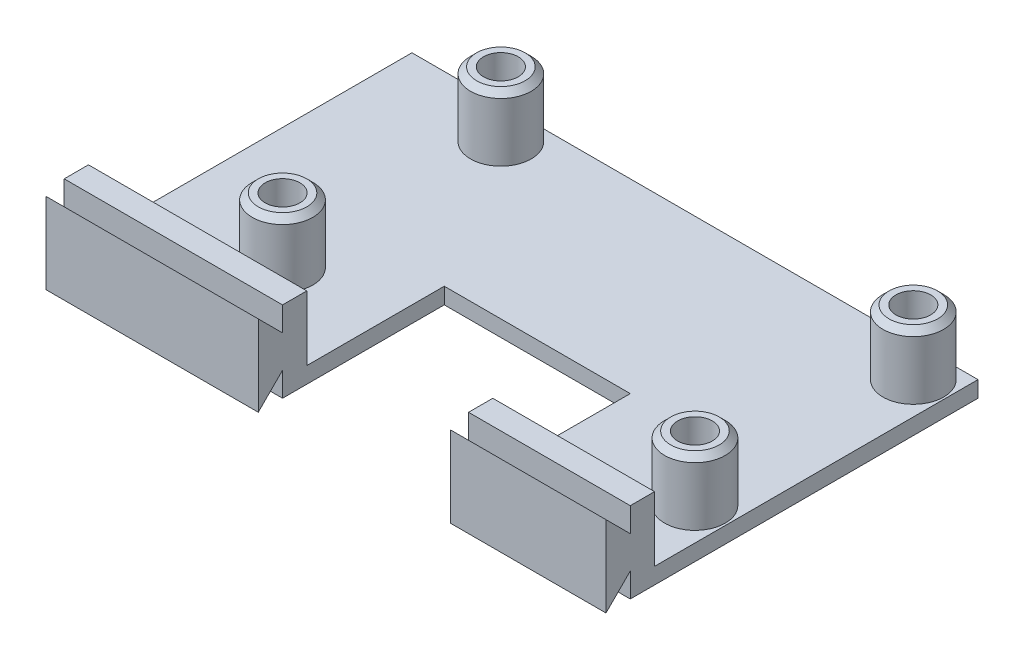
SolidWorks part; units mm, degrees
ref_plane "Front Plane" through (0, 0, 0) normal (0, 0, 1) x (1, 0, 0)
ref_plane "Top Plane" through (0, 0, 0) normal (0, 1, 0) x (1, 0, 0)
ref_plane "Right Plane" through (0, 0, 0) normal (1, 0, 0) x (0, 0, -1)
sketch "Sketch1" plane through (0, 0, 0) normal (0, 1, 0) x (1, 0, 0)
  line L1 (0, 0) -> (70, 0)
  line L2 (0, 0) -> (0, 35)
  line L3 (0, 35) -> (70, 35)
  line L4 (70, 0) -> (70, 35)
  dimension "D1" = 35
  dimension "D2" = 70
extrude "Boss-Extrude1" add sketch "Sketch1" along normal blind 2
sketch "Sketch2" plane through (0, 2, 0) normal (0, 1, 0) x (1, 0, 0)
  line L0 (70, 35) -> (0, 35) construction
  line L1 (70, 0) -> (70, 35) construction
  circle A0 centre (66, 31) radius 3.75
  circle A1 centre (15, 31) radius 3.75
  circle A2 centre (15, 4) radius 3.75
  circle A3 centre (66, 4) radius 3.75
  dimension "D1" = 2
  dimension "D3" = 51
  dimension "D4" = 27
  dimension "D5" = 4
  dimension "D6" = 4
  dimension "D7" = 7.5
  dimension "D2" = 2
extrude "Boss-Extrude2" add sketch "Sketch2" along normal blind 8
sketch "Sketch6" plane through (0, 0, 0) normal (0, 0, 1) x (1, 0, 0)
  line L4 (0, 0) -> (70, 0)
  line L5 (70, 0) -> (70, 2)
  line L6 (70, 2) -> (0, 2)
  line L7 (0, 2) -> (0, 0)
  line L8 (0, 0) -> (70, 0)
  line L9 (70, 0) -> (70, 2)
  line L10 (70, 2) -> (0, 2)
  line L11 (0, 2) -> (0, 0)
  dimension "D1" = 0
extrude "Boss-Extrude3" add sketch "Sketch6" along normal blind 2
hole_wizard "Ø4.3 (4.3) Diameter Hole1" positions "Sketch3" profile "Sketch4" hole size "Ø4.3" standard "DIN" end condition through all
sketch "Sketch3" plane through (0, 10, 0) normal (0, 1, 0) x (1, 0, 0)
  point P0 (66, 31)
  point P3 (15, 31)
  point P6 (15, 4)
  point P9 (66, 4)
sketch "Sketch4" plane through (66, 10, -31) normal (1, 0, 0) x (0, 0, 1)
  line L0 (0, 0) -> (0, 10)
  line L1 (0, 10) -> (2.15, 10)
  line L2 (2.15, 10) -> (2.15, 0)
  line L5 (2.15, 0) -> (0, 0)
  line L11 (0, -6.35) -> (0, 107.95) construction
  dimension "Thru Hole Dia." = 4.3
  dimension "Thru Hole Depth" = 10
chamfer "Chamfer1" distance 0.75 angle 45 4 edges at (15, 10, -0.25) (66, 10, -0.25) (66, 10, -27.25) (15, 10, -27.25)
sketch "Sketch5" plane through (0, 0, 0) normal (0, -1, 0) x (1, 0, 0)
  line L1 (27, -12) -> (50, -12)
  line L2 (27, -12) -> (27, 2)
  line L3 (27, 2) -> (50, 2)
  line L4 (50, -12) -> (50, 2)
  line L5 (27, -4) -> (15, -4) construction
  line L6 (50, -4) -> (66, -4) construction
  line L8 (0, 2) -> (70, 2) construction
  circle A4 centre (15, -4) radius 2.15 construction
  circle A5 centre (66, -4) radius 2.15 construction
  point P13 (0, 0)
  point P14 (23.5522, -32.5293)
  point P15 (0, 0)
  point P16 (0, 0)
  point P17 (0, 0)
  point P18 (0, 0)
  point P19 (0, 0)
  point P22 (0, 0)
  dimension "D1" = 14
  dimension "D2" = 12
  dimension "D3" = 16
extrude "Cut-Extrude1" cut sketch "Sketch5" against normal through all
fillet "Fillet1" [suppressed] radius 3
chamfer "Chamfer2" [suppressed] distance 2 angle 45
sketch "Sketch7" plane through (0, 0, 2) normal (0, 0, 1) x (1, 0, 0)
  line L0 (27, 0) -> (27, 2) construction
  line L1 (27, 2) -> (0, 2) construction
  line L2 (0, 2) -> (0, 0) construction
  line L3 (0, 0) -> (27, 0) construction
  line L4 (50, 2) -> (50, 0) construction
  line L5 (50, 0) -> (70, 0) construction
  line L6 (70, 0) -> (70, 2) construction
  line L7 (70, 2) -> (50, 2) construction
  line L8 (27, 0) -> (27, 2)
  line L9 (27, 2) -> (0, 2)
  line L10 (0, 2) -> (0, 0)
  line L11 (0, 0) -> (27, 0)
  line L12 (50, 2) -> (50, 0)
  line L13 (50, 0) -> (70, 0)
  line L14 (70, 0) -> (70, 2)
  line L15 (70, 2) -> (50, 2)
extrude "Boss-Extrude4" add sketch "Sketch7" along normal blind 3
sketch "Sketch9" plane through (0, 0, 5) normal (0, 0, 1) x (1, 0, 0)
  line L0 (70, 0) -> (70, 2) construction
  line L1 (0, 0) -> (27, 0)
  line L2 (0, 0) -> (0, 10)
  line L3 (0, 10) -> (27, 10)
  line L4 (27, 0) -> (27, 10)
  line L5 (50, 0) -> (70, 0)
  line L6 (50, 0) -> (50, 10)
  line L7 (50, 10) -> (70, 10)
  line L8 (70, 0) -> (70, 10)
  line L9 (27, 2) -> (27, 0) construction
  line L10 (18, 10) -> (12, 10) construction
extrude "Boss-Extrude5" add sketch "Sketch9" along normal blind 3
sketch "Sketch10" plane through (70, 0, 0) normal (1, 0, 0) x (0, 0, -1)
  line L0 (-8, 7) -> (-11, 10)
  line L1 (-8, 0) -> (-8, 10) construction
  line L2 (-11, 10) -> (-11, 0)
  line L3 (-11, 0) -> (-8, 3)
  line L4 (-8, 3) -> (-8, 7)
  line L5 (-8, 10) -> (-8, 7) construction
  line L6 (-8, 3) -> (-8, 0) construction
  line L7 (-8, 10) -> (-11, 10) construction
  line L8 (-8, 0) -> (-11, 0) construction
  dimension "D3" = 3
extrude "Boss-Extrude6" add sketch "Sketch10" against normal up to surface (20 mm away) up to face at (50, 4, 0.3333)
extrude "Boss-Extrude7" add sketch "Sketch10<2>" against normal up to surface (70 mm away) from surface up to face at (0, 4, -7.3333) starting at face at (27, 4, 0.3333)
sketch "Sketch10<2>" plane through (70, 0, 0) normal (1, 0, 0) x (0, 0, -1) same geometry as "Sketch10"
chamfer "Chamfer3" distance 0.75 angle 45 6 edges at (50, 8.5, 9.5) (50, 5, 11) (50, 1.5, 9.5) (0, 8.5, 9.5) (0, 5, 11) (0, 1.5, 9.5)
